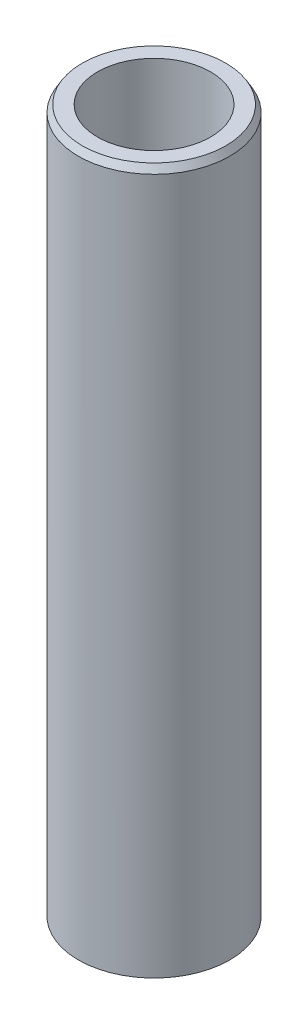
SolidWorks part; units mm, degrees
ref_plane "Front Plane" through (0, 0, 0) normal (0, 0, 1) x (1, 0, 0)
ref_plane "Top Plane" through (0, 0, 0) normal (0, 1, 0) x (1, 0, 0)
ref_plane "Right Plane" through (0, 0, 0) normal (1, 0, 0) x (0, 0, -1)
sketch "Sketch1" plane through (0, 0, 0) normal (0, 1, 0) x (1, 0, 0)
  circle A0 centre (0, 0) radius 52.5
  dimension "SHAFT_OD" = 105
extrude "Boss-Extrude1" add sketch "Sketch1" along normal blind 490.1107
sketch "Sketch2" plane through (0, 0, 0) normal (0, 1, 0) x (1, 0, 0)
  circle A0 centre (0, 0) radius 39.1931
  dimension "BORE_D" = 78.3862
extrude "Cut-Extrude1" cut sketch "Sketch2" along normal through all
chamfer "Chamfer1" distance 4.8524 angle 30 2 edges at (0, 490.1107, 52.5) (0, 0, 52.5) first distance on face at (0, 490.1107, 52.5) first distance on face at (0, 0, 39.1931)
